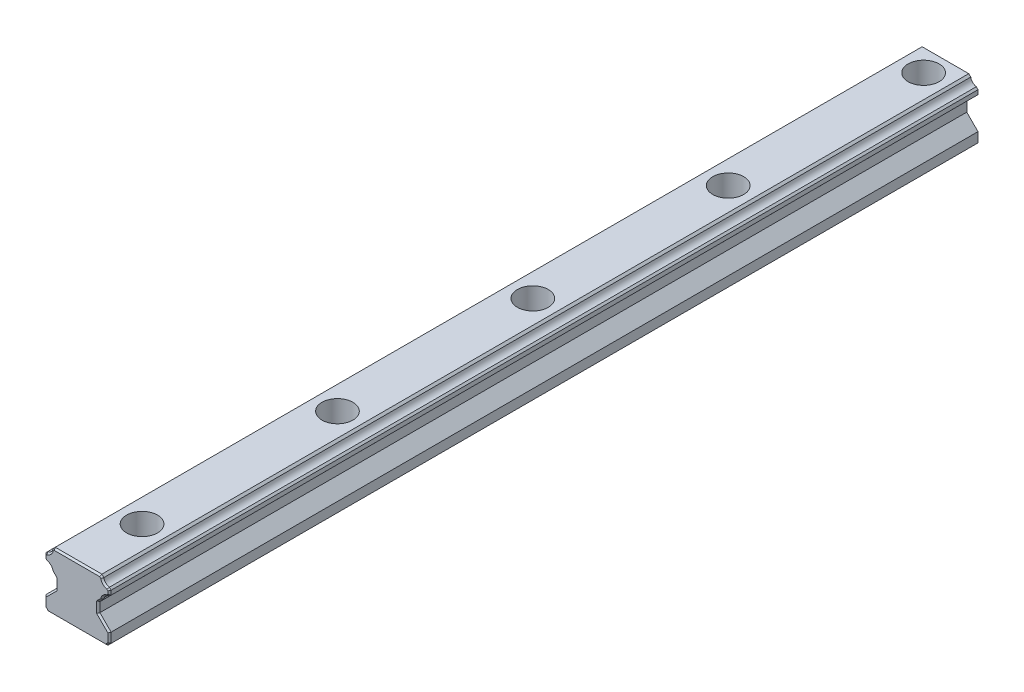
SolidWorks part; units mm, degrees
ref_plane "Front Plane" through (0, 0, 0) normal (0, 0, 1) x (1, 0, 0)
ref_plane "Top Plane" through (0, 0, 0) normal (0, 1, 0) x (1, 0, 0)
ref_plane "Right Plane" through (0, 0, 0) normal (1, 0, 0) x (0, 0, -1)
sketch "Sketch1" plane through (-20, 0, 0) normal (0, 0, 1) x (1, 0, 0)
  line L0 (10, -4.9999) -> (10, -8)
  line L1 (10, -8) -> (11, -9)
  line L2 (11, -9) -> (20, -9)
  line L3 (17, 9) -> (23, 9)
  line L5 (26.55, -1.55) -> (30, -4.9999)
  line L6 (26.55, 1.3792) -> (26.55, -1.55)
  line L7 (27.7679, 2.5951) -> (26.55, 1.3792)
  line L8 (30, 4.8292) -> (29.4727, 4.3144)
  line L9 (30, 6.16) -> (30, 4.8292)
  line L10 (29.4727, 6.6874) -> (30, 6.16)
  line L11 (27.16, 9) -> (27.7679, 8.3921)
  line L13 (29, -9) -> (20, -9)
  line L14 (30, -8) -> (29, -9)
  line L15 (30, -4.9999) -> (30, -8)
  line L16 (27.16, 9) -> (12.84, 9)
  line L17 (12.84, 9) -> (12.2321, 8.3921)
  line L18 (10.5273, 6.6874) -> (10, 6.16)
  line L19 (10, 6.16) -> (10, 4.8292)
  line L20 (10, 4.8292) -> (10.5273, 4.3144)
  line L21 (12.2321, 2.5951) -> (13.45, 1.3792)
  line L22 (13.45, 1.3792) -> (13.45, -1.55)
  line L23 (13.45, -1.55) -> (10, -4.9999)
  line L25 (20, -9) -> (20, 9) construction
  arc A0 (29.4727, 4.3144) -> (27.7679, 2.5951) centre (29.8039, 2.2812) ccw
  arc A1 (27.7679, 8.3921) -> (29.4727, 6.6874) centre (29.8015, 8.7209) ccw
  arc A2 (12.2321, 8.3921) -> (10.5273, 6.6874) centre (10.1985, 8.7209) cw
  arc A3 (10.5273, 4.3144) -> (12.2321, 2.5951) centre (10.1961, 2.2812) cw
  point P3 (20, 0.5)
  point P37 (20, 0)
  point P42 (20, 9)
  dimension "D17" = 2.06
  dimension "Rail Width" = 20
  dimension "D2" = 1
  dimension "D3" = 1
  dimension "D4" = 6
  dimension "D7" = 18
  dimension "D8" = 4.0001
  dimension "D9" = 10.55
  dimension "D10" = 13.1001
  dimension "D11" = 15.5359
  dimension "D12" = 0.6079
  dimension "D13" = 0.6079
  dimension "D15" = 0.5273
  dimension "D16" = 0.5273
  dimension "D18" = 1.2159
  dimension "D19" = 0.5148
  dimension "D20" = 6.4049
  dimension "D21" = 2.84
  dimension "D22" = 4.1708
  dimension "Rail Height" = 18
  dimension "Mounting Hole Dpeth" = 8.5
sketch "Sketch2" plane through (0, 0, 0) normal (1, 0, 0) x (0, 0, -1)
  line L0 (-120, 9) -> (-115.25, 9)
  line L1 (-115.25, 9) -> (-115.25, 0.5)
  line L2 (-115.25, 0.5) -> (-117, 0.5)
  line L3 (-117, 0.5) -> (-117, -9)
  line L4 (-117, -9) -> (-120, -9)
  line L5 (-120, -9) -> (-120, 9) construction
  line L6 (-120, -9) -> (-120, 9) construction
  line L7 (50, 0) -> (-50, 0)
  line L9 (-120, 9) -> (-120, -9)
  line L10 (140, 0) -> (-140, 0) construction
  point P6 (0, 0)
  point P7 (-120, 0)
  point P8 (60, 0)
  point P11 (0, 0)
  point P12 (-60, 0)
  point P14 (-50, 0)
  point P21 (0, 0)
  point P22 (50, 0)
  point P24 (120, 0)
  point P35 (50, -1)
  dimension "D1" = 9.5
  dimension "Rail Length" = 280
  dimension "Mounting Hole Center-to-End" = 20
  dimension "Mounting Hole Center-to-Center" = 60
  dimension "D2" = 90
  dimension "D4" = 1
  dimension "Number of Mounting Holes" = 5
sketch "Sketch3" plane through (0, 0, 0) normal (0, 0, 1) x (1, 0, 0)
  line L0 (-3, 9) -> (3, 9) construction
  line L3 (-3, 9) -> (3, 9)
  line L21 (0, -9) -> (9, -9)
  line L22 (9, -9) -> (10, -8)
  line L23 (10, -8) -> (10, -4.9999)
  line L24 (10, -4.9999) -> (6.55, -1.55)
  line L25 (6.55, -1.55) -> (6.55, 1.3792)
  line L26 (6.55, 1.3792) -> (7.7679, 2.5951)
  line L27 (9.4727, 4.3144) -> (10, 4.8292)
  line L28 (10, 4.8292) -> (10, 6.16)
  line L29 (10, 6.16) -> (9.4727, 6.6874)
  line L30 (7.7679, 8.3921) -> (7.16, 9)
  line L31 (7.16, 9) -> (-7.16, 9)
  line L32 (-7.16, 9) -> (-7.7679, 8.3921)
  line L33 (-9.4727, 6.6874) -> (-10, 6.16)
  line L34 (-10, 6.16) -> (-10, 4.8292)
  line L35 (-10, 4.8292) -> (-9.4727, 4.3144)
  line L36 (-7.7679, 2.5951) -> (-6.55, 1.3792)
  line L37 (-6.55, 1.3792) -> (-6.55, -1.55)
  line L38 (-6.55, -1.55) -> (-10, -4.9999)
  line L39 (-10, -4.9999) -> (-10, -8)
  line L40 (-10, -8) -> (-9, -9)
  line L41 (-9, -9) -> (0, -9)
  line L42 (0, -9) -> (9, -9)
  line L43 (9, -9) -> (10, -8)
  line L44 (10, -8) -> (10, -4.9999)
  line L45 (10, -4.9999) -> (6.55, -1.55)
  line L46 (6.55, -1.55) -> (6.55, 1.3792)
  line L47 (6.55, 1.3792) -> (7.7679, 2.5951)
  line L48 (9.4727, 4.3144) -> (10, 4.8292)
  line L49 (10, 4.8292) -> (10, 6.16)
  line L50 (10, 6.16) -> (9.4727, 6.6874)
  line L51 (7.7679, 8.3921) -> (7.16, 9)
  line L52 (7.16, 9) -> (-7.16, 9)
  line L53 (-7.16, 9) -> (-7.7679, 8.3921)
  line L54 (-9.4727, 6.6874) -> (-10, 6.16)
  line L55 (-10, 6.16) -> (-10, 4.8292)
  line L56 (-10, 4.8292) -> (-9.4727, 4.3144)
  line L57 (-7.7679, 2.5951) -> (-6.55, 1.3792)
  line L58 (-6.55, 1.3792) -> (-6.55, -1.55)
  line L59 (-6.55, -1.55) -> (-10, -4.9999)
  line L60 (-10, -4.9999) -> (-10, -8)
  line L61 (-10, -8) -> (-9, -9)
  line L62 (-9, -9) -> (0, -9)
  arc A4 (9.4727, 4.3144) -> (7.7679, 2.5951) centre (9.8039, 2.2812) ccw
  arc A5 (7.7679, 8.3921) -> (9.4727, 6.6874) centre (9.8015, 8.7209) ccw
  arc A6 (-9.4727, 6.6874) -> (-7.7679, 8.3921) centre (-9.8015, 8.7209) ccw
  arc A7 (-7.7679, 2.5951) -> (-9.4727, 4.3144) centre (-9.8039, 2.2812) ccw
  arc A8 (9.4727, 4.3144) -> (7.7679, 2.5951) centre (9.8039, 2.2812) ccw
  arc A9 (7.7679, 8.3921) -> (9.4727, 6.6874) centre (9.8015, 8.7209) ccw
  arc A10 (-9.4727, 6.6874) -> (-7.7679, 8.3921) centre (-9.8015, 8.7209) ccw
  arc A11 (-7.7679, 2.5951) -> (-9.4727, 4.3144) centre (-9.8039, 2.2812) ccw
  dimension "D1" = 0
extrude "Boss-Extrude1" add sketch "Sketch3" along normal up to vertex (140 mm away) and the other way up to vertex (140 mm away) contours A11 L57 L58 L59 L60 L61 L62 L42 L43 L44 L45 L46 L47 A8 L48 L49 L50 A9 L51 L52 L3 L53 A10 L54 L55 L56 region at (0, -0.2193, 0) up to point (0, 0, 140) other way up to point (0, 0, -140)
sketch "Sketch4" plane through (0, 0, 0) normal (1, 0, 0) x (0, 0, -1)
  line L6 (-115.25, 9) -> (-120, 9)
  line L7 (-115.25, 0.5) -> (-115.25, 9)
  line L8 (-117, 0.5) -> (-115.25, 0.5)
  line L9 (-117, -9) -> (-117, 0.5)
  line L10 (-120, -9) -> (-117, -9)
  line L11 (-120, 9) -> (-120, -9)
  line L12 (-115.25, 9) -> (-120, 9)
  line L13 (-115.25, 0.5) -> (-115.25, 9)
  line L14 (-117, 0.5) -> (-115.25, 0.5)
  line L15 (-117, -9) -> (-117, 0.5)
  line L16 (-120, -9) -> (-117, -9)
  line L17 (-120, 9) -> (-120, -9)
  dimension "D1" = 0
revolve "Cut-Revolve1" cut sketch "Sketch4" angle 360 about L17
pattern_linear "LPattern2" count 5 spacing 60 along (0, 0, -1) of "Cut-Revolve1"
sketch "Sketch5" plane through (0, 0, 0) normal (0, 1, 0) x (1, 0, 0)
  line L0 (3, -120) -> (0, -120) construction
  line L1 (0, -120) -> (2.1213, -117.8787) construction
  circle A1 centre (0, -120) radius 3 construction
  circle A2 centre (0, -120) radius 3 construction
  point P3 (0, -123)
  point P4 (-3, -120)
  point P6 (3, -120)
  point P7 (2.1213, -117.8787)
  dimension "D1" = 45
sketch "Sketch6" plane through (0, 0, 0) normal (0, 0, 1) x (1, 0, 0)
  line L0 (4.75, 9) -> (-4.75, 9) construction
  line L1 (3, 0.5) -> (-3, 0.5) construction
  line L2 (4.75, 9) -> (-4.75, 9) construction
  line L3 (3, 0.5) -> (-3, 0.5) construction
  line L4 (-4.75, 9) -> (-4.75, 0.5)
  line L5 (-4.75, 0.5) -> (-3, 0.5)
  line L6 (4.75, 9) -> (4.75, 0.5)
  line L7 (4.75, 0.5) -> (3, 0.5)
  line L8 (3, 0.5) -> (3, -9)
  line L9 (-9, -9) -> (9, -9) construction
  line L10 (-3, 0.5) -> (-3, -9)
chamfer "Chamfer1" distance 0.5 angle 45 48 edges at (-7.159, 1.9872, -140) (-6.55, -0.0854, -140) (-8.275, -3.275, -140) (-10, -6.5, -140) (-9.5, -8.5, -140) (0, -9, -140) (9.5, -8.5, -140) (10, -6.5, -140) (8.275, -3.275, -140) (6.55, -0.0854, -140) (7.159, 1.9872, -140) (8.3411, 3.7316, -140) (9.7363, 4.5718, -140) (10, 5.4946, -140) (9.7363, 6.4237, -140) (8.3449, 7.2643, -140) (7.464, 8.6961, -140) (0, 9, -140) (-7.464, 8.6961, -140) (-8.3449, 7.2643, -140) (-9.7363, 6.4237, -140) (-10, 5.4946, -140) (-9.7363, 4.5718, -140) (-8.3411, 3.7316, -140) (-9.7363, 4.5718, 140) (-10, 5.4946, 140) (-9.7363, 6.4237, 140) (-8.3449, 7.2643, 140) (-7.464, 8.6961, 140) (0, 9, 140) (7.464, 8.6961, 140) (8.3449, 7.2643, 140) (9.7363, 6.4237, 140) (10, 5.4946, 140) (9.7363, 4.5718, 140) (8.3411, 3.7316, 140) (7.159, 1.9872, 140) (6.55, -0.0854, 140) (8.275, -3.275, 140) (10, -6.5, 140) (9.5, -8.5, 140) (0, -9, 140) (-9.5, -8.5, 140) (-10, -6.5, 140) (-8.275, -3.275, 140) (-6.55, -0.0854, 140) (-7.159, 1.9872, 140) (-8.3411, 3.7316, 140)
sketch "Sketch7" plane through (0, -9, 0) normal (0, -1, 0) x (1, 0, 0)
  line L0 (15.69, -126.7) -> (-26.1609, -126.7)
  line L1 (-9.4958, -126.7) -> (-14.3167, -126.7) construction
extrude "Cut-Extrude1" cut sketch "Sketch7" against normal through all and the other way through all
equation "\"D3@LPattern2\"=\"Mounting Hole Center-to-Center@Sketch2\""
equation "\"D1@LPattern2\"=\"Number of Mounting Holes@Sketch2\""
